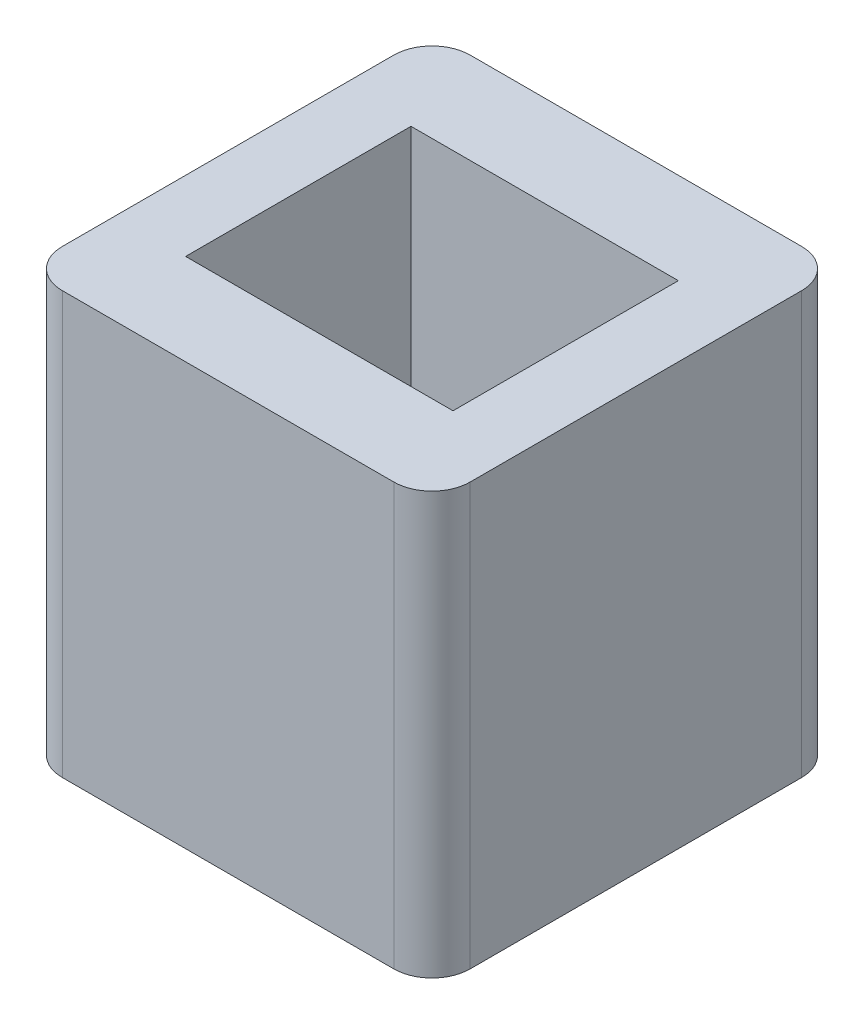
SolidWorks part; units mm, degrees
material "Copper"
ref_plane "Front Plane" through (0, 0, 0) normal (0, 0, 1) x (1, 0, 0)
ref_plane "Top Plane" through (0, 0, 0) normal (0, 1, 0) x (1, 0, 0)
ref_plane "Right Plane" through (0, 0, 0) normal (1, 0, 0) x (0, 0, -1)
sketch "Sketch1" plane through (0, 0, 0) normal (0, 1, 0) x (1, 0, 0)
  line L1 (-17.5, 14.75) -> (17.5, 14.75)
  line L2 (-17.5, 14.75) -> (-17.5, -14.75)
  line L3 (-17.5, -14.75) -> (17.5, -14.75)
  line L4 (17.5, 14.75) -> (17.5, -14.75)
  line L5 (-17.5, 14.75) -> (17.5, -14.75) construction
  line L6 (-17.5, -14.75) -> (17.5, 14.75) construction
  line L7 (-21.7, 26.7) -> (21.7, 26.7)
  line L8 (-26.7, 21.7) -> (-26.7, -21.7)
  line L9 (-21.7, -26.7) -> (21.7, -26.7)
  line L10 (26.7, 21.7) -> (26.7, -21.7)
  line L11 (-26.7, 26.7) -> (26.7, -26.7) construction
  line L12 (-26.7, -26.7) -> (26.7, 26.7) construction
  arc A0 (-21.7, -26.7) -> (-26.7, -21.7) centre (-21.7, -21.7) cw
  arc A1 (26.7, -21.7) -> (21.7, -26.7) centre (21.7, -21.7) cw
  arc A2 (26.7, 21.7) -> (21.7, 26.7) centre (21.7, 21.7) ccw
  arc A3 (-26.7, 21.7) -> (-21.7, 26.7) centre (-21.7, 21.7) cw
  point P0 (0, 0)
  point P5 (0, 0)
  dimension "D4" = 5
  dimension "D1" = 29.5
  dimension "D2" = 35
  dimension "D3" = 53.4
extrude "Boss-Extrude1" add sketch "Sketch1" along normal mid plane 55.2
